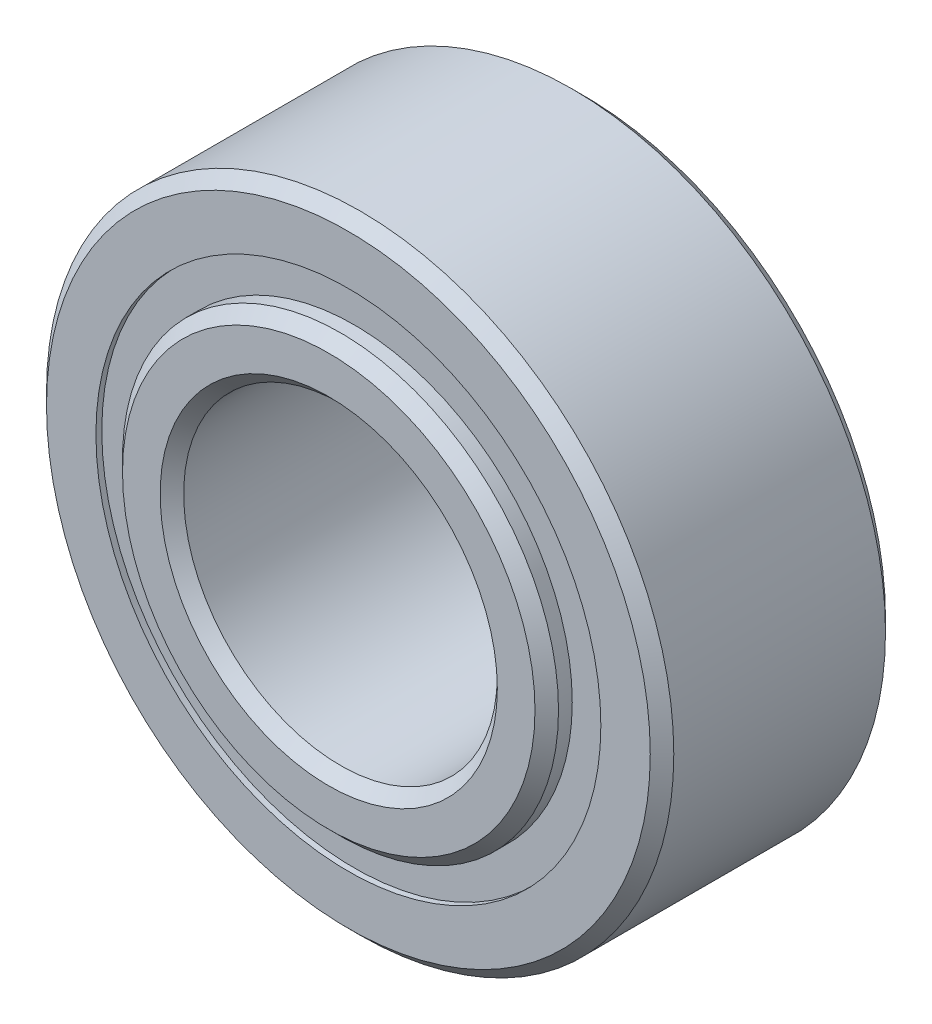
SolidWorks part; units mm, degrees
material "Cast Alloy Steel"
ref_plane "Front Plane" through (0, 0, 0) normal (0, 0, 1) x (1, 0, 0)
ref_plane "Top Plane" through (0, 0, 0) normal (0, 1, 0) x (1, 0, 0)
ref_plane "Right Plane" through (0, 0, 0) normal (1, 0, 0) x (0, 0, -1)
sketch "Sketch1" plane through (0, 0, 0) normal (1, 0, 0) x (0, 0, -1)
  line L0 (-2.3813, 0) -> (2.3813, 0) construction
  line L1 (0, 6.35) -> (0, -6.35) construction
  line L2 (2.1431, 6.35) -> (-2.1431, 6.35)
  line L3 (-2.1431, 6.35) -> (-2.3813, 6.1119)
  line L4 (-2.3813, 6.1119) -> (-2.3813, 5.1114)
  line L5 (-2.3813, 5.1114) -> (-1.0583, 5.1114)
  line L6 (2.3813, 5.1114) -> (1.0583, 5.1114)
  line L7 (2.3813, 6.1119) -> (2.3813, 5.1114)
  line L8 (2.1431, 6.35) -> (2.3813, 6.1119)
  line L9 (0, 6.35) -> (0, 4.7625) construction
  line L10 (0, 4.7625) -> (0, 3.175) construction
  arc A0 (-1.0583, 5.1114) -> (1.0583, 5.1114) centre (0, 4.7625) cw
  point P14 (0, 3.175)
  dimension "D3" = 2.1167
  dimension "D1" = 45
  dimension "Width" = 4.7625
  dimension "OD" = 12.7
  dimension "D2" = 0.2381
  dimension "Shaft Dia" = 6.35
  dimension "D4" = 0.3489
revolve "Revolve1" add sketch "Sketch1" angle 360 about L0
sketch "Sketch3" plane through (0, 0, 0) normal (1, 0, 0) x (0, 0, -1)
  line L0 (-1.0583, 4.4136) -> (-2.7788, 4.4136) construction
  line L1 (-2.3813, 6.1119) -> (-2.3813, 5.1114) construction
  line L2 (-2.1431, 6.35) -> (-2.3813, 6.1119) construction
  line L3 (-2.7788, 4.4136) -> (-2.7788, 3.4131) construction
  line L4 (-2.7788, 3.4131) -> (-2.7788, 4.1755)
  line L5 (-2.7788, 3.4131) -> (-2.5406, 3.175)
  line L6 (-2.5406, 3.175) -> (2.5406, 3.175)
  line L8 (2.5406, 3.175) -> (2.7788, 3.4131)
  line L10 (2.7788, 3.4131) -> (2.7788, 4.4136) construction
  line L11 (2.7788, 4.4136) -> (1.0583, 4.4136) construction
  line L12 (0, 6.35) -> (0, -6.35) construction
  line L13 (2.1431, 6.35) -> (2.3813, 6.1119) construction
  line L14 (-2.7788, 4.1755) -> (-2.5406, 4.4136)
  line L15 (-2.5406, 4.4136) -> (-1.0583, 4.4136)
  line L16 (1.0583, 4.4136) -> (2.5406, 4.4136)
  line L17 (2.5406, 4.4136) -> (2.7788, 4.1755)
  line L18 (2.7788, 4.1755) -> (2.7788, 3.4131)
  arc A1 (1.0583, 4.4136) -> (-1.0583, 4.4136) centre (0, 4.7625) cw
  arc A2 (1.0583, 5.1114) -> (-1.0583, 5.1114) centre (0, 4.7625) ccw construction
  dimension "D1" = 45
  dimension "Ring" = 5.5575
revolve "Revolve3" add sketch "Sketch3" angle 360 about L0
sketch "Sketch4" plane through (0, 0, 0) normal (1, 0, 0) x (0, 0, -1)
  line L0 (-1.1144, 4.7625) -> (1.1144, 4.7625)
  arc A2 (-1.1144, 4.7625) -> (1.1144, 4.7625) centre (0, 4.7625) cw
  arc A3 (1.0583, 5.1114) -> (-1.0583, 5.1114) centre (0, 4.7625) ccw construction
revolve "Revolve4" add sketch "Sketch4" angle 360 about L0
ref_axis "Axis1" through (0, 0, -2.3813) along (0, 0, 1)
pattern_circular "CirPattern1" count 10 every 36 about axis through (0, 0, -2.3813) along (0, 0, 1) of bodies 104
sketch "Sketch5" plane through (0, 0, 0) normal (1, 0, 0) x (0, 0, -1)
  line L0 (-2.3813, 5.1114) -> (-1.0583, 5.1114) construction
  line L1 (-2.2622, 5.1114) -> (-1.1144, 5.1114)
  line L2 (-2.2622, 5.1114) -> (-2.2622, 4.4136)
  line L3 (-2.2622, 4.4136) -> (-1.1144, 4.4136)
  line L4 (-1.1144, 5.1114) -> (-1.1144, 4.4136)
  line L5 (-1.0583, 4.4136) -> (-2.7788, 4.4136) construction
  line L6 (2.3813, 5.1114) -> (1.0583, 5.1114) construction
  line L7 (2.2622, 5.1114) -> (1.1144, 5.1114)
  line L8 (2.2622, 5.1114) -> (2.2622, 4.4136)
  line L9 (2.2622, 4.4136) -> (1.1144, 4.4136)
  line L10 (1.1144, 5.1114) -> (1.1144, 4.4136)
  line L11 (2.7788, 4.4136) -> (1.0583, 4.4136) construction
  line L12 (-2.1431, 6.35) -> (-2.3813, 6.1119) construction
  point P18 (-2.2622, 6.2309)
revolve "Revolve5" add sketch "Sketch5" angle 360 about L0
equation "\"D2@Sketch1\" = \"Width@Sketch1\"*.05"
equation "\"D3@Sketch1\" = \"Width@Sketch1\"/2.25"
equation "\"D4@Sketch1\" = (((\"OD@Sketch1\"-\"Width@Sketch1\")/2)/3.25)/3.5"
equation "\"D2@CirPattern1\" = 360/\"Balls@CirPattern1\""
